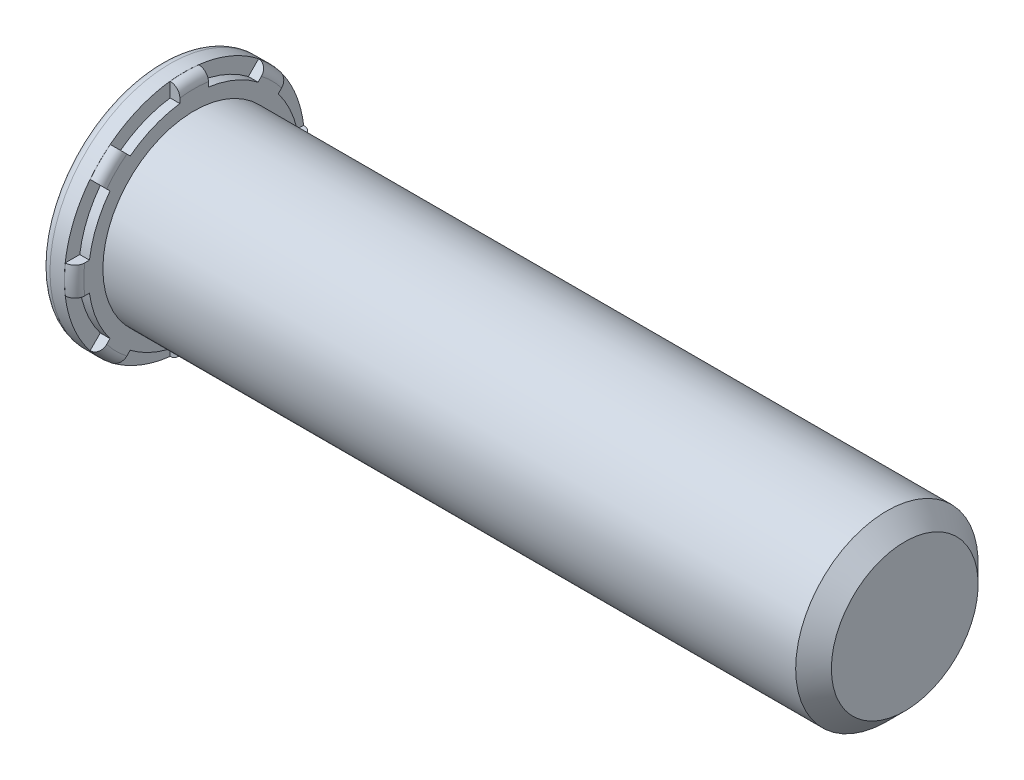
SolidWorks part; units mm, degrees
revolve "BaseBody" add sketch "BodySke" angle 360 about L6 other way angle 7.5
sketch "BodySke" plane through (0, 0, 0) normal (0, 0, 1) x (1, 0, 0)
  line L0 (-0.635, 2.921) -> (-0.635, 0)
  line L1 (0.2565, 2.9185) -> (0.2565, 2.413)
  line L3 (0.2565, 2.413) -> (18.5776, 2.413)
  line L4 (19.05, 1.9406) -> (19.05, 0)
  line L5 (19.05, 0) -> (-0.635, 0)
  line L6 (0, 0) -> (50.554, 0) construction
  line L8 (19.05, 1.9406) -> (18.5776, 2.413)
  line L9 (-0.381, 3.175) -> (0, 3.175)
  line L10 (0.0025, 3.1725) -> (0, 3.1725)
  line L11 (0.7925, 19.05) -> (0.7925, -3.175) construction
  line L12 (0, 3.1725) -> (0, 3.175)
  arc A0 (-0.635, 2.921) -> (-0.381, 3.175) centre (-0.381, 2.921) cw
  arc A1 (0.0025, 3.1725) -> (0.2565, 2.9185) centre (0.0025, 2.9185) cw
  dimension "Fillet_rad" = 0.254
  dimension "Minor_dia" = 3.8811
  dimension "Diameter" = 4.826
  dimension "T_dim" = 0.635
  dimension "H_dia" = 6.35
  dimension "D2" = 0.0025
  dimension "D3" = 0.0025
  dimension "Length" = 19.05
  dimension "Advance" = 0.7925
cosmetic thread "ThreadCosmetic" [suppressed] parameters "Thread_length"=16.764, "Thread_minor"=3.8811
ref_plane "Plane1" through (0, 0, 0) normal (0, 0, 1) x (1, 0, 0)
ref_plane "Plane2" through (0, 0, 0) normal (0, 1, 0) x (1, 0, 0)
ref_plane "Plane3" through (0, 0, 0) normal (1, 0, 0) x (0, 0, -1)
sketch "ThdSchSke" plane through (0, 0, 0) normal (0, 0, 1) x (1, 0, 0)
  line L0 (2.286, -1.9406) -> (1.9552, -2.413)
  line L1 (2.286, -1.9406) -> (2.6168, -2.413)
  line L2 (2.6168, -2.413) -> (2.6168, -3.0162)
  line L3 (-3.175, 0) -> (5.1513, 0) construction
  line L4 (0, -3.175) -> (0, 3.175) construction
  line L5 (2.6168, -3.0162) -> (1.9552, -3.0162)
  line L6 (1.9552, -3.0162) -> (1.9552, -2.413)
  dimension "Diameter" = 4.826
  dimension "Thread_minor" = 3.8811
  dimension "Start" = 2.286
revolve "ThreadSchematic" [suppressed] cut sketch "ThdSchSke" angle 360 about L3
pattern_linear "ThdSchPat" [suppressed]
sketch "RibCutSke" plane through (0.2565, 1.7944, -0.091) normal (1, 0, 0) x (0, 0, -1)
  line L0 (0.2865, 0.974) -> (0.2865, 1.3581)
  line L1 (1.5997, 0.4301) -> (1.8713, 0.7017)
  line L2 (0.2865, 0.5889) -> (0.2865, 2.4006) construction
  line L3 (-0.091, -1.7944) -> (-0.091, 5.0239) construction
  line L4 (-0.091, -1.7944) -> (0.2865, 0.5889) construction
  line L5 (-0.091, -1.7944) -> (1.3274, 0.1578) construction
  line L6 (1.3274, 0.1578) -> (2.6135, 1.4439) construction
  circle A0 centre (-0.091, -1.7944) radius 2.9185 construction
  arc A1 (1.5997, 0.4301) -> (0.2865, 0.974) centre (-0.091, -1.7944) ccw
  arc A2 (1.8713, 0.7017) -> (0.2865, 1.3581) centre (-0.091, -1.7944) ccw
  circle A4 centre (-0.091, -1.7944) radius 2.413 construction
  dimension "Rib_root_half_angle" = 9
  dimension "Rib_root_gap_angle" = 27
  dimension "Angle" = 45
extrude "RibCut" cut sketch "RibCutSke" against normal blind 0.2565
pattern_circular "RibCutsPat" count 8 every 45 about axis through (0, 0, 0) along (1, 0, 0) of "RibCut"
equation "' \"Length@BodySke\" = 0.75"
equation "' \"H_dia@BodySke\" = 0.25"
equation "' \"Start@ThdSchSke\" = 0.09"
equation "' \"T_dim@BodySke\" = 0.025"
equation "' \"Diameter@BodySke\" = 0.19"
equation "' \"Minor_dia@BodySke\" = 0.1528"
equation "' \"Advance@BodySke\" = 0.0312"
equation "\"Fillet_rad@BodySke\" =  \"T_dim@BodySke\" * 0.4"
equation "\"Num_ribs@RibCutsPat\" = 8"
equation "\"Angle@RibCutSke\" =\"Angle@RibCutsPat\""
equation "\"Rib_root_half_angle@RibCutSke\" = \"Angle@RibCutSke\" / 5"
equation "\"Rib_root_gap_angle@RibCutSke\" = \"Angle@RibCutSke\" - (2 * \"Rib_root_half_angle@RibCutSke\" )"
equation "\"Rib_root_dia@RibCutSke\" = \"Diameter@BodySke\""
equation "\"Inner_dia@RibCutSke\" = ( \"H_dia@BodySke\" + \"Diameter@BodySke\" ) / 2"
equation "\"Outer_dia@RibCutSke\" = \"H_dia@BodySke\""
equation "\"Depth@RibCut\" =  \"Fillet_rad@BodySke\" + 0.0001"
equation "\"Thread_length@ThreadCosmetic\" = \"Length@BodySke\" - \"Start@ThdSchSke\""
equation "\"Thread_minor@ThreadCosmetic\" = \"Minor_dia@BodySke\""
equation "\"Thread_minor@ThdSchSke\" = \"Minor_dia@BodySke\""
equation "\"Diameter@ThdSchSke\" = \"Diameter@BodySke\""
equation "\"Overcut@ThdSchSke\" = \"Diameter@BodySke\" * 1.25"
equation "\"Num_threads@ThdSchPat\" = int( \"Thread_length@ThreadCosmetic\" / \"Advance@BodySke\" + 0.999 )  + 1"
equation "\"Advance@ThdSchPat\" = \"Thread_length@ThreadCosmetic\" /  (\"Num_threads@ThdSchPat\" - 1) 'relax it"
equation "\"Num_threads@ThdSchPat\" = \"Num_threads@ThdSchPat\" - sgn( \"Num_threads@ThdSchPat\" - 1) '---chamfered tips only---"
